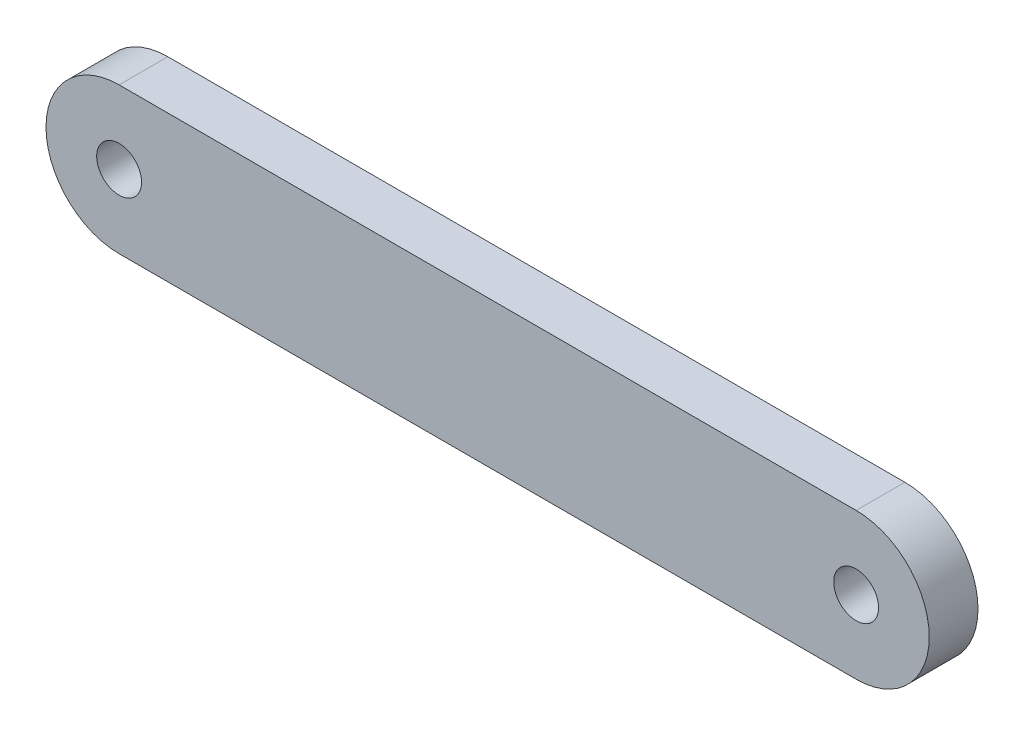
SolidWorks part; units mm, degrees
ref_plane "前视基准面" through (0, 0, 0) normal (0, 0, 1) x (1, 0, 0)
ref_plane "上视基准面" through (0, 0, 0) normal (0, 1, 0) x (1, 0, 0)
ref_plane "右视基准面" through (0, 0, 0) normal (1, 0, 0) x (0, 0, -1)
other "Configuration Table"
sketch "草图1" plane through (0, 0, 0) normal (0, 0, 1) x (1, 0, 0)
  line L1 (-37.8, 7.5) -> (37.8, 7.5)
  line L3 (-37.8, -7.5) -> (37.8, -7.5)
  line L5 (-37.8, 7.5) -> (37.8, -7.5) construction
  line L6 (-37.8, -7.5) -> (37.8, 7.5) construction
  arc A0 (-37.8, 7.5) -> (-37.8, -7.5) centre (-37.8, 0) ccw
  arc A1 (37.8, 7.5) -> (37.8, -7.5) centre (37.8, 0) cw
  circle A2 centre (-37.8, 0) radius 2.3
  circle A3 centre (37.8, 0) radius 2.3
  point P0 (0, 0)
  dimension "D1" = 4.6
  dimension "D2" = 4.6
  dimension "D3" = 75.6
  dimension "D4" = 15
extrude "凸台-拉伸1" add sketch "草图1" along normal blind 5
equation "\"fi\"=4.6"
equation "\"D1@草图1\"=\"fi\""
equation "\"D2@草图1\"=\"fi\""
equation "\"b0\"= 75.6'ground"
equation "\"D3@草图1\"=\"b0\""
equation "\"width\"=15"
equation "\"D4@草图1\"=\"width\""
equation "\"depth\"=5"
equation "\"D1@凸台-拉伸1\"=\"depth\""
equation "\"b1\"= \"b0\" *1.4/ 2'rocker"
equation "\"b2\"= \"b0\"'coupler"
equation "\"b3\"= \"b0\" / 2'coupler"
equation "\"b4\"= \"b0\" *2'leg"
equation "\"angle\"= 90度'左右cranker夹角"
equation "\"b5\"=(\"b2\"^2+\"b4\"^2)^0.5'斜边"
